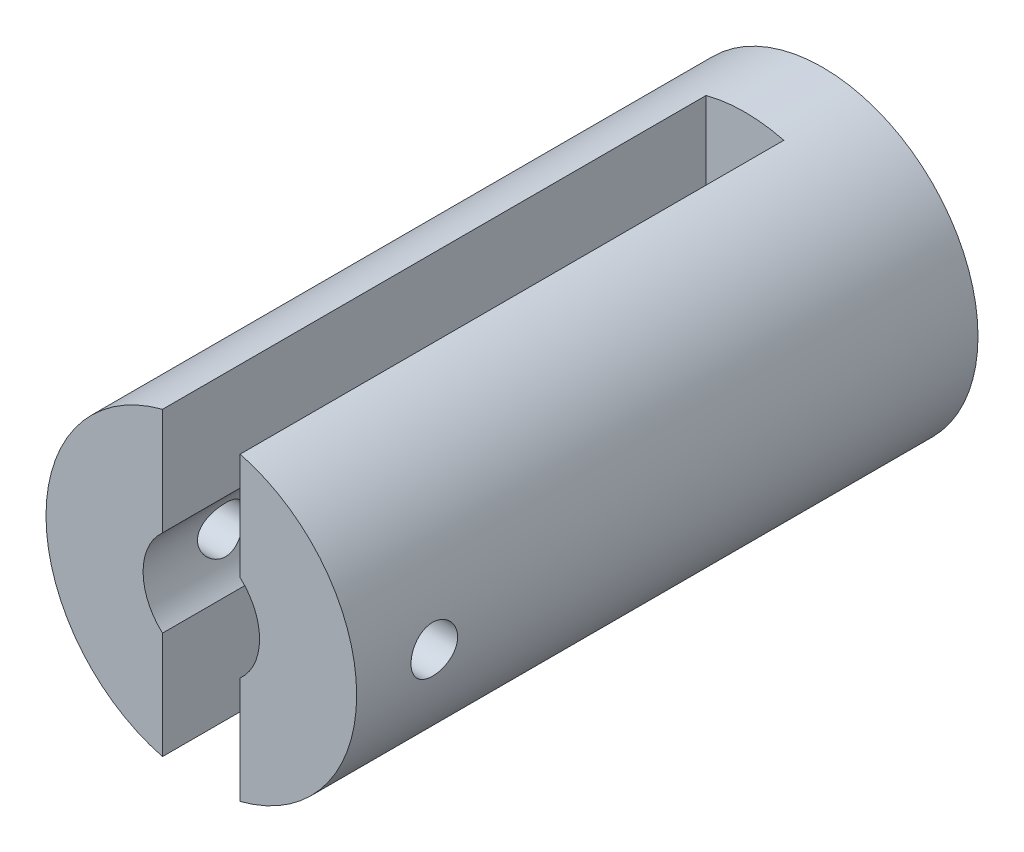
SolidWorks part; units mm, degrees
ref_plane "Alzado" through (0, 0, 0) normal (0, 0, 1) x (1, 0, 0)
ref_plane "Planta" through (0, 0, 0) normal (0, 1, 0) x (1, 0, 0)
ref_plane "Vista lateral" through (0, 0, 0) normal (1, 0, 0) x (0, 0, -1)
sketch "Croquis1" plane through (0, 0, 0) normal (0, 0, 1) x (1, 0, 0)
  circle A0 centre (0, 0) radius 2.25
  circle A1 centre (0, 0) radius 10
  dimension "D1" = 4.5
  dimension "D2" = 20
extrude "Saliente-Extruir1" add sketch "Croquis1" along normal blind 5
sketch "Croquis2" plane through (0, 0, 5) normal (0, 0, 1) x (1, 0, 0)
  line L2 (-2.5, -9.6825) -> (-2.5, 9.6825)
  line L4 (2.5, -9.6825) -> (2.5, 9.6825)
  circle A0 centre (0, 0) radius 10 construction
  arc A1 (2.5, -9.6825) -> (2.5, 9.6825) centre (0, 0) ccw
  arc A2 (-2.5, 9.6825) -> (-2.5, -9.6825) centre (0, 0) ccw
  dimension "D1" = 2.5
  dimension "D2" = 5
extrude "Saliente-Extruir2" add sketch "Croquis2" along normal blind 35
sketch "Croquis3" plane through (2.5, 0, 0) normal (-1, 0, 0) x (0, 0, 1)
  line L0 (0, 0) -> (40, 0) construction
  line L1 (40, -9.6825) -> (40, 9.6825) construction
  circle A0 centre (35, 0) radius 1.5
  dimension "D1" = 3
  dimension "D2" = 5
extrude "Cortar-Extruir1" cut sketch "Croquis3" against normal mid plane 40
sketch "Croquis4" plane through (0, 0, 5) normal (0, 0, 1) x (1, 0, 0)
  circle A0 centre (0, 0) radius 3.75
  dimension "D1" = 7.5
extrude "Cortar-Extruir2" cut sketch "Croquis4" against normal blind 2.5
sketch "Croquis6" plane through (0, 0, 2.5) normal (0, 0, 1) x (1, 0, 0)
  circle A1 centre (0, 0) radius 3.75
  circle A2 centre (0, 0) radius 3.75
  dimension "D1" = 0
extrude "Cortar-Extruir4" cut sketch "Croquis6" along normal blind 49
